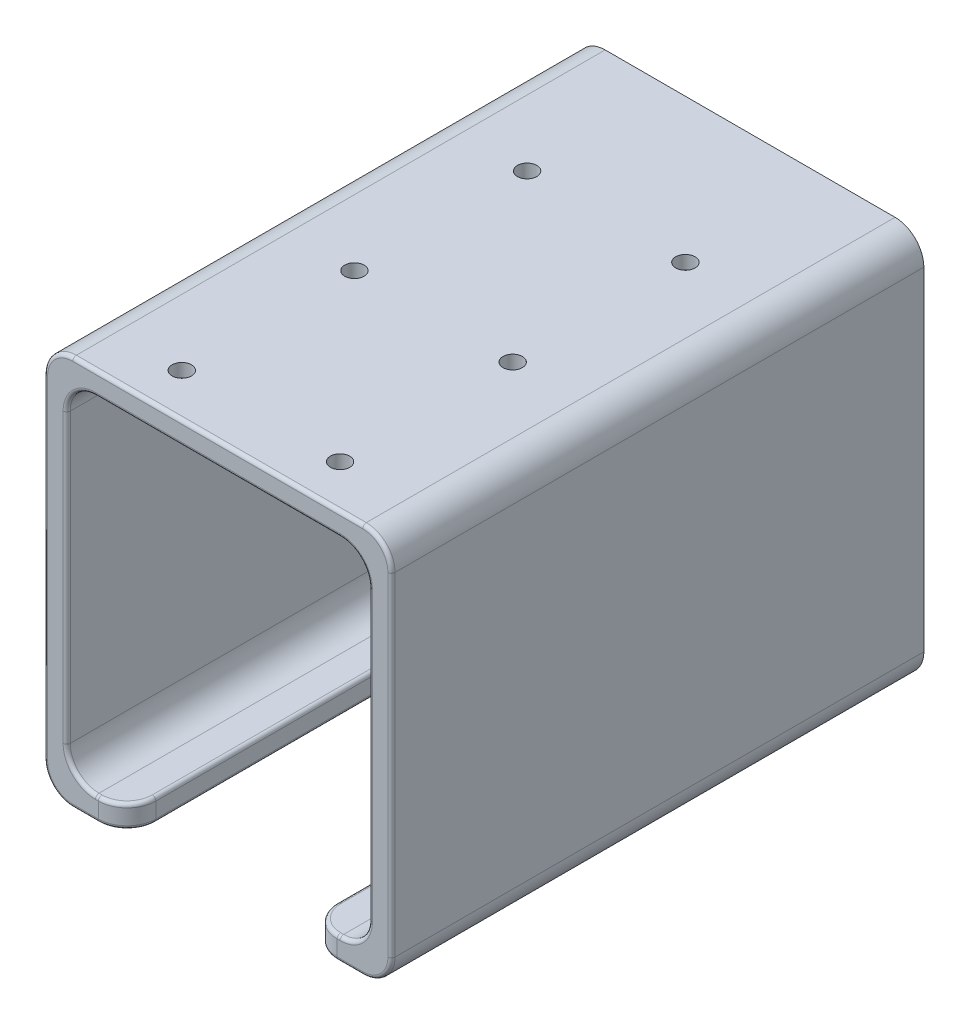
SolidWorks part; units mm, degrees
ref_plane "Front Plane" through (0, 0, 0) normal (0, 0, 1) x (1, 0, 0)
ref_plane "Top Plane" through (0, 0, 0) normal (0, 1, 0) x (1, 0, 0)
ref_plane "Right Plane" through (0, 0, 0) normal (1, 0, 0) x (0, 0, -1)
sketch "Sketch2" plane through (0, 0, 0) normal (0, 0, 1) x (1, 0, 0)
  line L0 (-38.3375, 0) -> (-33.3375, 0) construction
  line L1 (-33.3375, -38.1) -> (33.3375, -38.1)
  line L2 (-33.3375, -38.1) -> (-33.3375, 38.1)
  line L3 (-33.3375, 38.1) -> (33.3375, 38.1)
  line L4 (33.3375, -38.1) -> (33.3375, 38.1)
  line L5 (-33.3375, -38.1) -> (33.3375, 38.1) construction
  line L6 (-33.3375, 38.1) -> (33.3375, -38.1) construction
  line L7 (-38.3375, -43.1) -> (38.3375, -43.1)
  line L8 (-38.3375, -43.1) -> (-38.3375, 43.1)
  line L9 (-38.3375, 43.1) -> (38.3375, 43.1)
  line L10 (38.3375, -43.1) -> (38.3375, 43.1)
  line L11 (-38.3375, -43.1) -> (38.3375, 43.1) construction
  line L12 (-38.3375, 43.1) -> (38.3375, -43.1) construction
  line L13 (0, 38.1) -> (0, 43.1) construction
  point P0 (0, 0)
  point P6 (0, 0)
  dimension "D1" = 5
  dimension "D2" = 66.675
  dimension "D3" = 76.2
extrude "Boss-Extrude1" add sketch "Sketch2" along normal blind 152.4
sketch "Sketch3" plane through (0, -43.1, 0) normal (0, -1, 0) x (1, 0, 0)
  line L0 (0, 152.4) -> (0, 70.8) construction
  line L1 (-38.3375, 152.4) -> (38.3375, 152.4) construction
  line L2 (20, 152.4) -> (20, 70.8)
  line L3 (-20, 152.4) -> (-20, 70.8)
  arc A0 (20, 152.4) -> (-20, 152.4) centre (0, 152.4) ccw
  arc A1 (-20, 70.8) -> (20, 70.8) centre (0, 70.8) ccw
  point P5 (0, 111.6)
  point P10 (0, 50.8)
  dimension "D1" = 40
  dimension "D2" = 101.6
extrude "Cut-Extrude1" cut sketch "Sketch3" against normal up to next
fillet "Fillet1" radius 6.35 10 edges at (-38.3375, 43.1, 76.2) (-38.3375, -43.1, 76.2) (38.3375, -43.1, 76.2) (38.3375, 43.1, 76.2) (33.3375, 38.1, 76.2) (-33.3375, 38.1, 76.2) (-33.3375, -38.1, 76.2) (33.3375, -38.1, 76.2) (20, -40.6, 152.4) (-20, -40.6, 152.4)
sketch "Sketch5" plane through (0, 38.1, 0) normal (0, -1, 0) x (1, 0, 0)
  line L0 (-26.9875, 142.875) -> (-17.4625, 142.875) construction
  line L1 (-26.9875, 152.4) -> (-26.9875, 0) construction
  line L2 (-17.4625, 142.875) -> (-17.4625, 152.4) construction
  line L3 (26.9875, 152.4) -> (-26.9875, 152.4) construction
  circle A0 centre (-17.4625, 142.875) radius 2.1399
  dimension "D2" = 4.2799
  dimension "D1" = 9.525
extrude "Cut-Extrude2" cut sketch "Sketch5" against normal through all
ref_axis "Axis1" through (-17.4625, 43.1, 142.875) along (0, -1, 0)
ref_plane "Plane1" through (-17.4625, 0, 0) normal (-1, 0, 0) x (0, -1, 0)
sketch "Sketch6" plane through (-17.4625, 0, 0) normal (-1, 0, 0) x (0, -1, 0)
  line L0 (-38.1, 138.7475) -> (-38.1, 142.875)
  line L2 (-43.1, 142.875) -> (-38.1, 142.875) construction
  line L3 (-38.1, 142.875) -> (-42.2275, 142.875) construction
  line L4 (-42.2275, 142.875) -> (-38.1, 138.7475)
  line L5 (-38.1, 142.875) -> (-42.2275, 142.875)
  line L6 (-38.1, 152.4) -> (-38.1, 0) construction
  dimension "D1" = 45
  dimension "D2" = 8.255
revolve "Cut-Revolve1" cut sketch "Sketch6" angle 360 about L3
pattern_linear "LPattern1" count 4 spacing 38.1 along (0, 0, -1) of "Cut-Extrude2", "Cut-Revolve1"
mirror "Mirror3" about plane through (0, 0, 0) normal (1, 0, 0) of "LPattern1", "Cut-Revolve1", "Cut-Extrude2"
sketch "Sketch7" plane through (0, 0, 0) normal (0, 0, -1) x (-1, 0, 0)
  line L4 (38.3375, -36.75) -> (38.3375, 36.75)
  line L5 (31.9875, 43.1) -> (-31.9875, 43.1)
  line L6 (-38.3375, 36.75) -> (-38.3375, -36.75)
  line L7 (-31.9875, -43.1) -> (31.9875, -43.1)
  line L8 (38.3375, -36.75) -> (38.3375, 36.75)
  line L9 (31.9875, 43.1) -> (-31.9875, 43.1)
  line L10 (-38.3375, 36.75) -> (-38.3375, -36.75)
  line L11 (-31.9875, -43.1) -> (31.9875, -43.1)
  arc A4 (38.3375, 36.75) -> (31.9875, 43.1) centre (31.9875, 36.75) ccw
  arc A5 (-31.9875, 43.1) -> (-38.3375, 36.75) centre (-31.9875, 36.75) ccw
  arc A6 (-38.3375, -36.75) -> (-31.9875, -43.1) centre (-31.9875, -36.75) ccw
  arc A7 (31.9875, -43.1) -> (38.3375, -36.75) centre (31.9875, -36.75) ccw
  arc A8 (38.3375, 36.75) -> (31.9875, 43.1) centre (31.9875, 36.75) ccw
  arc A9 (-31.9875, 43.1) -> (-38.3375, 36.75) centre (-31.9875, 36.75) ccw
  arc A10 (-38.3375, -36.75) -> (-31.9875, -43.1) centre (-31.9875, -36.75) ccw
  arc A11 (31.9875, -43.1) -> (38.3375, -36.75) centre (31.9875, -36.75) ccw
  dimension "D1" = 0
extrude "Cut-Extrude3" cut sketch "Sketch7" against normal blind 34.925
fillet "Fillet2" radius 0.7937 28 edges at (-21.8599, -43.1, 150.5401) (-29.1687, -43.1, 152.4) (-36.4776, -41.2401, 152.4) (-38.3375, 0, 152.4) (-36.4776, 41.2401, 152.4) (0, 43.1, 152.4) (36.4776, 41.2401, 152.4) (38.3375, 0, 152.4) (36.4776, -41.2401, 152.4) (29.1688, -43.1, 152.4) (21.8599, -43.1, 150.5401) (20, -43.1, 108.425) (0, -43.1, 50.8) (-20, -38.1, 108.425) (-21.8599, -38.1, 150.5401) (-26.6688, -38.1, 152.4) (-31.4776, -36.2401, 152.4) (-33.3375, 0, 152.4) (-31.4776, 36.2401, 152.4) (0, 38.1, 152.4) (31.4776, 36.2401, 152.4) (33.3375, 0, 152.4) (31.4776, -36.2401, 152.4) (26.6688, -38.1, 152.4) (21.8599, -38.1, 150.5401) (20, -38.1, 108.425) (-20, -43.1, 108.425) (0, -38.1, 50.8)
